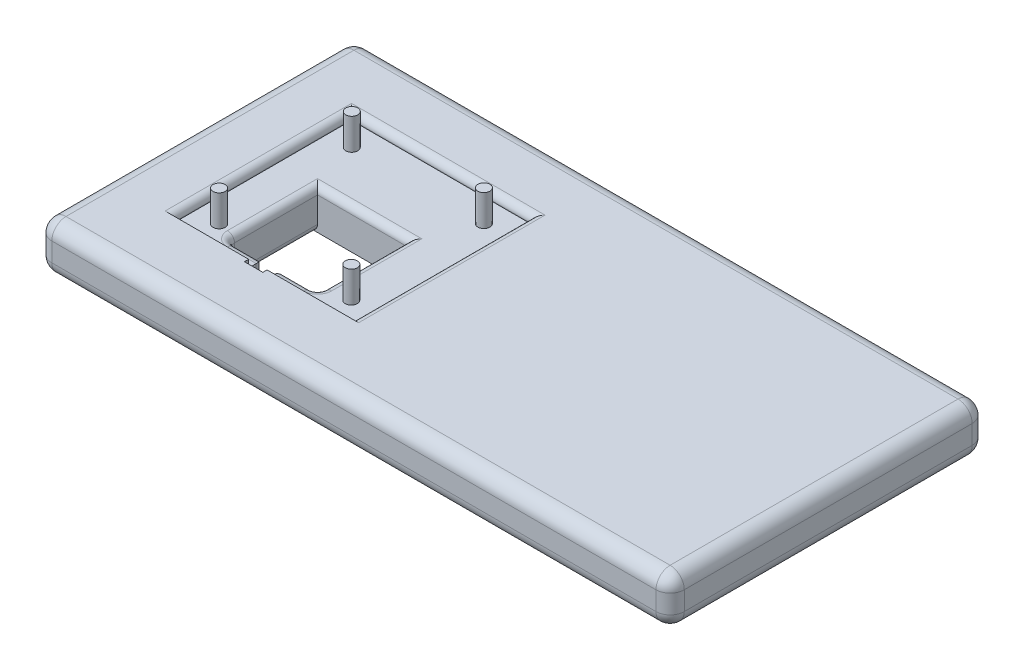
SolidWorks part; units mm, degrees
ref_plane "Front Plane" through (0, 0, 0) normal (0, 0, 1) x (1, 0, 0)
ref_plane "Top Plane" through (0, 0, 0) normal (0, 1, 0) x (1, 0, 0)
ref_plane "Right Plane" through (0, 0, 0) normal (1, 0, 0) x (0, 0, -1)
sketch "Sketch1" plane through (0, 0, 0) normal (0, 1, 0) x (1, 0, 0)
  line L1 (-25.7879, 23.097) -> (108.2121, 23.097)
  line L2 (-25.7879, 23.097) -> (-25.7879, -43.903)
  line L3 (-25.7879, -43.903) -> (108.2121, -43.903)
  line L4 (108.2121, 23.097) -> (108.2121, -43.903)
  dimension "D1" = 67
  dimension "D2" = 134
extrude "Boss-Extrude1" add sketch "Sketch1" along normal blind 10
sketch "Sketch2" plane through (0, 10, 0) normal (0, 1, 0) x (1, 0, 0)
  line L0 (7.2121, 8.597) -> (7.2121, -29.403) construction
  line L1 (-11.7879, 8.597) -> (26.2121, 8.597)
  line L2 (-11.7879, 8.597) -> (-11.7879, -29.403)
  line L3 (-11.7879, -29.403) -> (26.2121, -29.403)
  line L4 (26.2121, 8.597) -> (26.2121, -29.403)
  line L5 (-6.7879, 3.647) -> (21.2121, 3.647) construction
  line L6 (-6.7879, 3.647) -> (-6.7879, -24.453) construction
  line L7 (-6.7879, -24.453) -> (21.2121, -24.453) construction
  line L8 (21.2121, 3.647) -> (21.2121, -24.453) construction
  line L9 (-11.7879, -10.403) -> (26.2121, -10.403) construction
  line L10 (41.2121, 23.097) -> (41.2121, -43.903) construction
  line L11 (-3.1879, -7.203) -> (15.9121, -7.203)
  line L12 (-3.1879, -7.203) -> (-3.1879, -26.303)
  line L13 (-3.1879, -26.303) -> (15.9121, -26.303)
  line L14 (15.9121, -7.203) -> (15.9121, -26.303)
  line L15 (4.4121, -26.303) -> (8.3121, -26.303)
  line L16 (4.4121, -26.303) -> (4.4121, -30.303)
  line L17 (4.4121, -30.303) -> (8.3121, -30.303)
  line L18 (8.3121, -26.303) -> (8.3121, -30.303)
  line L19 (108.2121, 23.097) -> (-25.7879, 23.097) construction
  line L20 (-25.7879, -43.903) -> (108.2121, -43.903) construction
  line L21 (-25.7879, 23.097) -> (-25.7879, -43.903) construction
  line L22 (-25.7879, -10.403) -> (108.2121, -10.403) construction
  line L23 (108.2121, -43.903) -> (108.2121, 23.097) construction
  circle A0 centre (-6.7879, 3.647) radius 1.275
  circle A1 centre (21.2121, 3.647) radius 1.275
  circle A2 centre (21.2121, -24.453) radius 1.275
  circle A3 centre (-6.7879, -24.453) radius 1.275
  point P12 (7.2121, 3.647)
  point P13 (21.2121, -10.403)
  point P26 (6.3621, -26.303)
  point P27 (6.3621, -26.303)
  dimension "D5" = 2.55
  dimension "D1" = 38
  dimension "D2" = 38
  dimension "D3" = 28.1
  dimension "D4" = 28
  dimension "D6" = 19.1
  dimension "D7" = 19.1
  dimension "D8" = 8.6
  dimension "D9" = 3.9
  dimension "D10" = 3.1
  dimension "D11" = 4
  dimension "D12" = 15
extrude "Cut-Extrude1" cut sketch "Sketch2" against normal up to surface (10 mm away) contours L14 L11 L12 L13 region at (6.3621, 10, 16.753) up to face at (41.2121, 0, 10.403)
extrude "Boss-Extrude2" add sketch "Sketch2<3>" along normal blind 5 contours A0 | A3 | A2 | A1 region at (-6.7879, 10, -3.647) region at (21.2121, 10, -3.647) region at (21.2121, 10, 24.453) region at (-6.7879, 10, 24.453)
sketch "Sketch2<3>" plane through (0, 10, 0) normal (0, 1, 0) x (1, 0, 0) same geometry as "Sketch2"
extrude "Cut-Extrude3" cut sketch "Sketch2<6>" against normal blind 1.6 contours L13 L18 L3 L4 L1 L2 L16 L12 L11 L14 A3 A2 A1 A0 region at (7.2121, 10, -8.0596)
sketch "Sketch2<6>" plane through (0, 10, 0) normal (0, 1, 0) x (1, 0, 0) same geometry as "Sketch2"
extrude "Cut-Extrude2" cut sketch "Sketch2<5>" against normal blind 3.14 contours L18 L13 L16 L3 | L18 L3 L16 L17 region at (6.3621, 10, 27.853) region at (6.3621, 10, 29.853)
sketch "Sketch2<5>" plane through (0, 10, 0) normal (0, 1, 0) x (1, 0, 0) same geometry as "Sketch2"
fillet "Fillet1" radius 3 12 edges at (41.2121, 10, 43.903) (41.2121, 0, 43.903) (108.2121, 5, 43.903) (108.2121, 10, 10.403) (108.2121, 0, 10.403) (108.2121, 5, -23.097) (41.2121, 10, -23.097) (41.2121, 0, -23.097) (-25.7879, 5, -23.097) (-25.7879, 10, 10.403) (-25.7879, 5, 43.903) (-25.7879, 0, 10.403)
fillet "Fillet2" radius 1.5 13 edges at (-3.1879, 0, 16.753) (15.9121, 0, 16.753) (6.3621, 6.86, 26.303) (4.4121, 7.63, 26.303) (0.6121, 8.4, 26.303) (-3.1879, 4.2, 26.303) (6.3621, 0, 26.303) (15.9121, 4.2, 26.303) (12.1121, 8.4, 26.303) (8.3121, 7.63, 26.303) (-3.1879, 8.4, 16.753) (6.3621, 8.4, 7.203) (15.9121, 8.4, 16.753)
fillet "Fillet3" radius 1.5 3 edges at (26.2121, 10, 10.403) (-11.7879, 10, 10.403) (7.2121, 10, -8.597)
